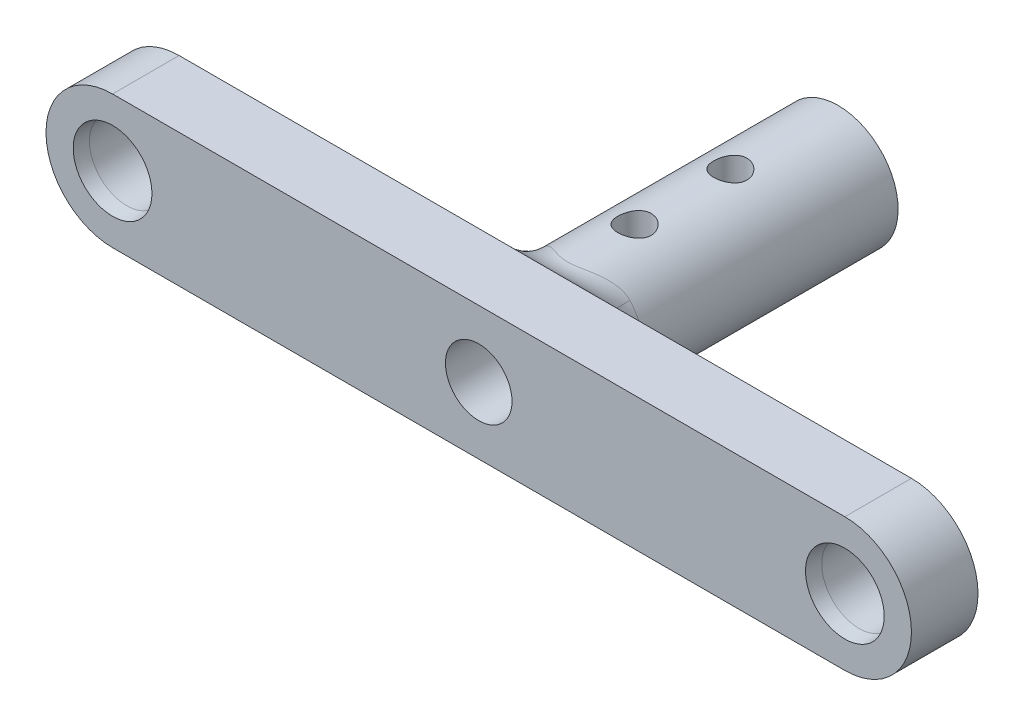
SolidWorks part; units mm, degrees
ref_plane "Front Plane" through (0, 0, 0) normal (0, 0, 1) x (1, 0, 0)
ref_plane "Top Plane" through (0, 0, 0) normal (0, 1, 0) x (1, 0, 0)
ref_plane "Right Plane" through (0, 0, 0) normal (1, 0, 0) x (0, 0, -1)
sketch "Sketch1" plane through (0, 0, 0) normal (0, 0, 1) x (1, 0, 0)
  circle B0 centre (-4.9732, 1.4895) radius 2.5
  circle B1 centre (22.5268, 1.4895) radius 2.8067
  circle B2 centre (-32.4732, 1.4895) radius 2.8067
  line B3 (-32.4732, 6.4895) -> (22.5268, 6.4895)
  arc B4 (22.5268, -3.5105) -> (22.5268, 6.4895) centre (22.5268, 1.4895) ccw
  line B5 (-32.4732, -3.5105) -> (22.5268, -3.5105)
  arc B6 (-32.4732, 6.4895) -> (-32.4732, -3.5105) centre (-32.4732, 1.4895) ccw
  line B7 (-32.4732, 1.4895) -> (22.5268, 1.4895) construction
sketch_block_instance "Block-center_link-1"
sketch_block "Block-center_link" parameters "D1"=5.6134, "D2"=5.6134, "D3"=5, "D4"=55, "D5"=10
extrude "Boss-Extrude1" add sketch "Sketch1" along normal blind 5
sketch "Sketch2" plane through (0, 0, 0) normal (0, 0, -1) x (-1, 0, 0)
  circle A0 centre (4.9732, 1.4895) radius 4.5
  circle A1 centre (4.9732, 1.4895) radius 2.4973
extrude "Boss-Extrude2" add sketch "Sketch2" along normal blind 22
fillet "Fillet1" radius 3 1 edges at (-0.4732, 1.4895, 0)
hole_wizard "Tap Drill for M3x0.5 Tap1" positions "Sketch4" profile "Sketch5" hole size "M3x0.5" standard "ANSI Metric" end condition up to next
sketch "Sketch4" plane through (0, 0, 0) normal (0, 1, 0) x (1, 0, 0)
  line L0 (-4.9732, -21.079) -> (-4.9732, 21.079) construction
  line L1 (22.5268, -5) -> (-32.4732, -5) construction
  point P22 (-4.9732, 13.8995)
  point P24 (-4.9732, 6.7058)
  point P35 (-4.9732, -5)
sketch "Sketch5" plane through (-4.9732, 0, -6.7058) normal (1, 0, 0) x (0, 0, -1)
  line L0 (0, 0) -> (0, 5.9895)
  line L1 (0, 5.9895) -> (1.25, 5.9895)
  line L2 (1.25, 5.9895) -> (1.25, 0)
  line L5 (1.25, 0) -> (0, 0)
  line L11 (0, -6.35) -> (0, 107.95) construction
  dimension "Thru Hole Dia." = 2.5
  dimension "Thru Hole Depth" = 5.9895
chamfer "Chamfer1" distance 0.15 angle 82 2 edges at (25.3335, 1.4895, 5) (-29.6665, 1.4895, 5) first distance on face at (25.3335, 1.4895, 5)
